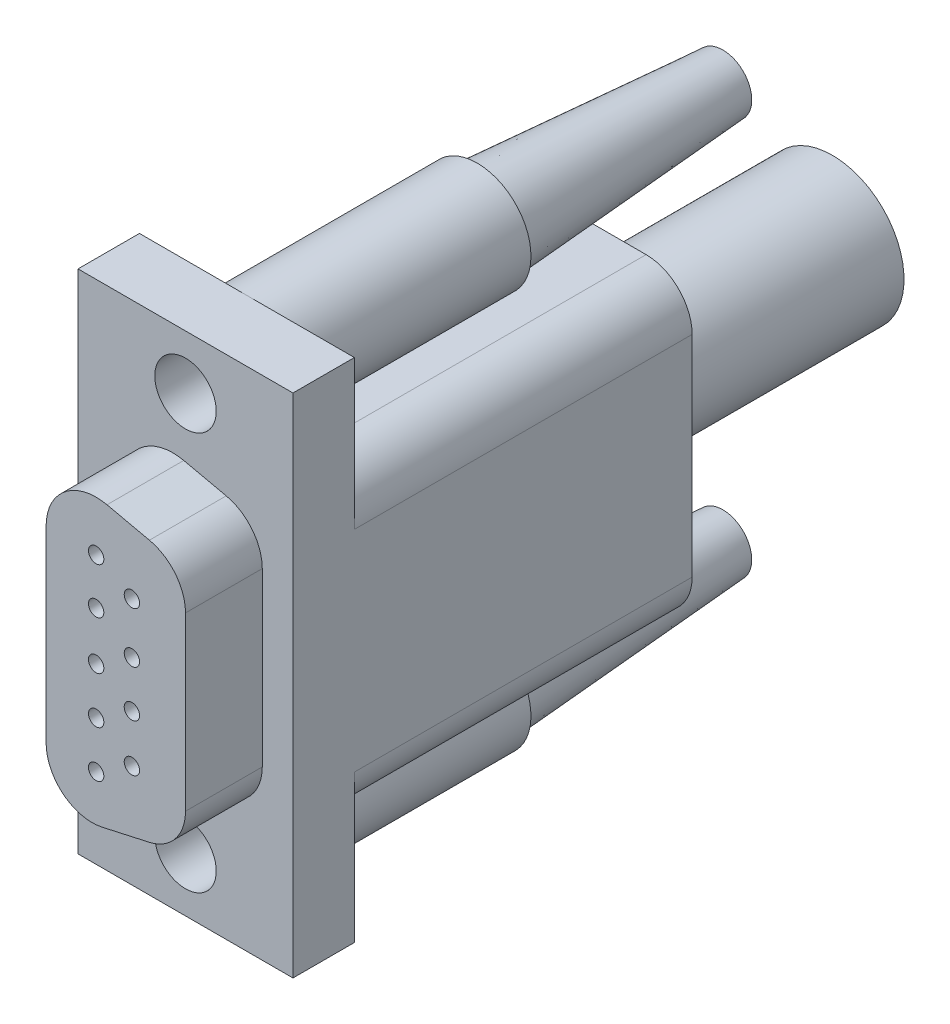
SolidWorks part; units mm, degrees
ref_plane "前视基准面" through (0, 0, 0) normal (0, 0, 1) x (1, 0, 0)
ref_plane "上视基准面" through (0, 0, 0) normal (0, 1, 0) x (1, 0, 0)
ref_plane "右视基准面" through (0, 0, 0) normal (1, 0, 0) x (0, 0, -1)
sketch "草图2" plane through (0, 0, 0) normal (0, 0, 1) x (1, 0, 0)
  line L0 (15.641, 15.2434) -> (15.641, 3.0095)
  line L1 (24.7197, 3.6937) -> (24.7197, 14.8806)
  line L2 (19.6055, 18.4236) -> (22.3705, 17.8092)
  line L3 (19.2918, 0.0809) -> (22.3705, 0.7651)
  line L5 (12.7197, 9.2871) -> (12.7197, 25.7871)
  line L6 (12.7197, 25.7871) -> (26.7197, 25.7871)
  line L7 (26.7197, 25.7871) -> (26.7197, -7.2129)
  line L8 (26.7197, -7.2129) -> (12.7197, -7.2129)
  line L9 (12.7197, -7.2129) -> (12.7197, 9.2871)
  circle A0 centre (19.7197, -3.6813) radius 2
  arc A1 (19.6055, 18.4236) -> (15.641, 15.2434) centre (18.8988, 15.2434) ccw
  arc A2 (15.641, 3.0095) -> (19.2918, 0.0809) centre (18.641, 3.0095) ccw
  arc A3 (24.7197, 3.6937) -> (22.3705, 0.7651) centre (21.7197, 3.6937) cw
  arc A4 (24.7197, 14.8806) -> (22.3705, 17.8092) centre (21.7197, 14.8806) ccw
  circle A5 centre (19.7197, 22.2558) radius 2
  circle A6 centre (18.8988, 15.2434) radius 0.5
  circle A7 centre (18.8988, 12.2434) radius 0.5
  circle A8 centre (18.8988, 9.0966) radius 0.5
  circle A9 centre (18.8988, 6.0481) radius 0.5
  circle A10 centre (18.8988, 3.0095) radius 0.5
  circle A11 centre (21.2284, 13.9293) radius 0.5
  circle A12 centre (21.2284, 10.6211) radius 0.5
  circle A13 centre (21.2284, 7.5887) radius 0.5
  circle A14 centre (21.2284, 4.4949) radius 0.5
extrude "凸台-拉伸1" add sketch "草图2" along normal blind 5 contours L0 A2 L3 A3 L1 A4 L2 A1
extrude "切除-拉伸1" cut sketch "草图2<5>" along normal blind 6 contours A10 | A9 | A8 | A7 | A11 | A6 | A14 | A13 | A12
sketch "草图2<5>" plane through (0, 0, 0) normal (0, 0, 1) x (1, 0, 0) same geometry as "草图2"
extrude "凸台-拉伸2" add sketch "草图2<6>" against normal blind 4 contours L7 L8 L9 L5 L6
sketch "草图2<6>" plane through (0, 0, 0) normal (0, 0, 1) x (1, 0, 0) same geometry as "草图2"
extrude "切除-拉伸2" cut sketch "草图2<8>" against normal blind 4 contours A0 | A5
sketch "草图2<8>" plane through (0, 0, 0) normal (0, 0, 1) x (1, 0, 0) same geometry as "草图2"
sketch "草图3" plane through (0, 0, -4) normal (0, 0, -1) x (-1, 0, 0)
  circle A0 centre (-19.7197, 22.2558) radius 3.5
  circle A1 centre (-19.7197, -3.6813) radius 3.5
extrude "凸台-拉伸3" add sketch "草图3" along normal blind 15
sketch "草图4" plane through (0, 0, -4) normal (0, 0, -1) x (-1, 0, 0)
  line L0 (-23.7197, 19.0916) -> (-15.7197, 19.0916)
  line L1 (-26.7197, 25.7871) -> (-26.7197, -7.2129) construction
  line L2 (-12.7197, 9.2871) -> (-12.7197, 25.7871) construction
  line L3 (-23.7197, -0.5972) -> (-15.7197, -0.5972)
  line L4 (-12.7197, -7.2129) -> (-12.7197, 9.2871) construction
  line L5 (-26.7197, 16.0916) -> (-26.7197, 2.4028)
  line L6 (-12.7197, 16.0916) -> (-12.7197, 2.4028)
  arc A0 (-23.7197, 19.0916) -> (-26.7197, 16.0916) centre (-23.7197, 16.0916) ccw
  arc A1 (-12.7197, 16.0916) -> (-15.7197, 19.0916) centre (-15.7197, 16.0916) ccw
  arc A2 (-26.7197, 2.4028) -> (-23.7197, -0.5972) centre (-23.7197, 2.4028) ccw
  arc A3 (-15.7197, -0.5972) -> (-12.7197, 2.4028) centre (-15.7197, 2.4028) ccw
  point P12 (-26.7197, 19.0916)
  point P15 (-12.7197, 19.0916)
  point P18 (-26.7197, -0.5972)
  point P21 (-12.7197, -0.5972)
  dimension "D1" = 3
  dimension "D2" = 3
  dimension "D3" = 3
  dimension "D4" = 3
extrude "凸台-拉伸4" add sketch "草图4" along normal blind 22 contours A0 L5 A2 L3 A3 L6 A1 L0
sketch "草图5" plane through (0, 0, -19) normal (0, 0, -1) x (-1, 0, 0)
  circle A0 centre (-19.7197, 22.2558) radius 3
extrude "凸台-拉伸5" add sketch "草图5" along normal blind 16 draft 4
sketch "草图6" plane through (0, 0, -19) normal (0, 0, -1) x (-1, 0, 0)
  circle A0 centre (-19.7197, -3.6813) radius 3
extrude "凸台-拉伸6" add sketch "草图6" along normal blind 16 draft 4
sketch "草图7" plane through (0, 0, -26) normal (0, 0, -1) x (-1, 0, 0)
  circle A0 centre (-19.8553, 10.1004) radius 4.6637
extrude "凸台-拉伸7" add sketch "草图7" along normal blind 16
